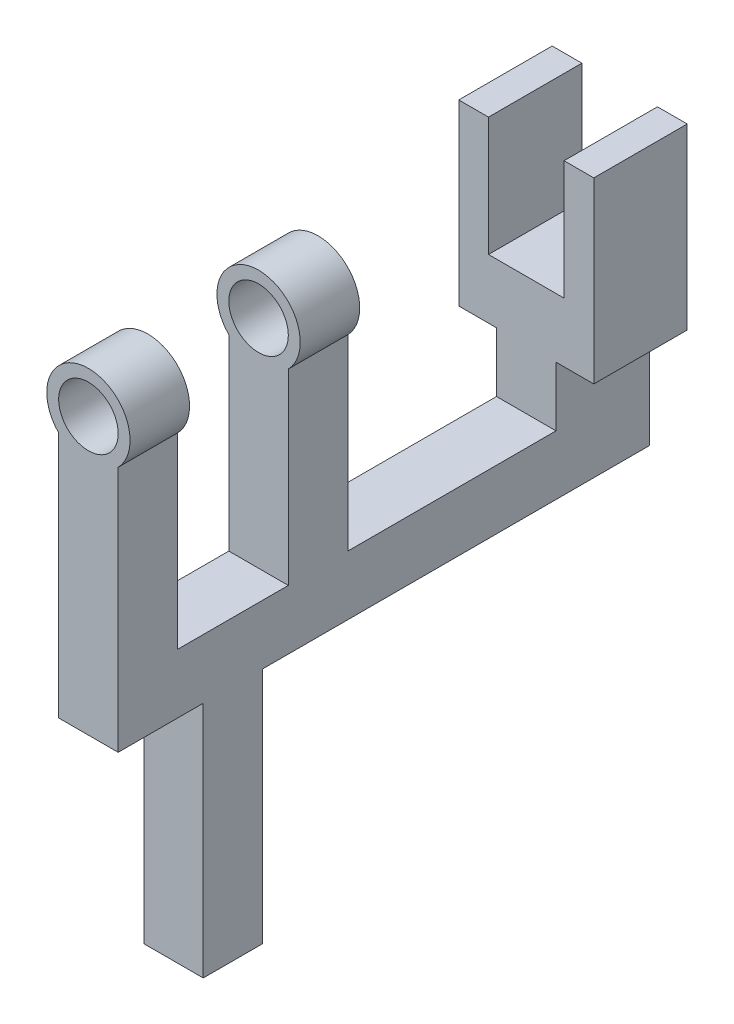
SolidWorks part; units mm, degrees
ref_plane "Front Plane" through (0, 0, 0) normal (0, 0, 1) x (1, 0, 0)
ref_plane "Top Plane" through (0, 0, 0) normal (0, 1, 0) x (1, 0, 0)
ref_plane "Right Plane" through (0, 0, 0) normal (1, 0, 0) x (0, 0, -1)
sketch "Sketch1" plane through (0, 0, 0) normal (0, 0, 1) x (1, 0, 0)
  line L1 (0, 0) -> (-10, 0)
  line L2 (0, 0) -> (0, -10)
  line L3 (0, -10) -> (-10, -10)
  line L4 (-10, 0) -> (-10, -10)
  dimension "D1" = 10
  dimension "D2" = 10
extrude "Boss-Extrude1" add sketch "Sketch1" along normal blind 70 contours L4 L3 L2 L1
sketch "Sketch2" plane through (0, 0, 0) normal (0, 1, 0) x (1, 0, 0)
  line L0 (-10, -70) -> (-10, 0) construction
  line L1 (0, 0) -> (-10, 0)
  line L2 (0, 0) -> (0, -15.7)
  line L3 (0, -15.7) -> (-10, -15.7)
  line L4 (-10, 0) -> (-10, -15.7)
  dimension "D1" = 15.7
extrude "Boss-Extrude2" add sketch "Sketch2" along normal blind 20
sketch "Sketch3" plane through (0, 20, 0) normal (0, 1, 0) x (1, 0, 0)
  line L0 (-10, 0) -> (0, 0)
  line L1 (-10, 0) -> (-11.35, 0)
  line L2 (0, 0) -> (1.35, 0)
  line L4 (-10, 0) -> (-10, -15.7)
  line L5 (-10, -15.7) -> (0, -15.7)
  line L6 (0, -15.7) -> (0, 0)
  line L7 (-11.35, 0) -> (-11.35, -15.7)
  line L8 (-11.35, -15.7) -> (-10, -15.7)
  line L9 (0, -15.7) -> (1.35, -15.7)
  line L10 (1.35, -15.7) -> (1.35, 0)
  line L11 (-11.35, 0) -> (-16.35, 0)
  line L12 (-16.35, 0) -> (-16.35, -15.7)
  line L13 (-16.35, -15.7) -> (-11.35, -15.7)
  line L14 (1.35, 0) -> (6.35, 0)
  line L15 (6.35, 0) -> (6.35, -15.7)
  line L16 (6.35, -15.7) -> (1.35, -15.7)
  point P3 (-5, 0)
  dimension "D1" = 12.7
  dimension "D2" = 5
extrude "Boss-Extrude4" add sketch "Sketch3" along normal blind 20 and the other way blind 10 separate body contours L12 L13 L7 L11 | L16 L15 L14 L10 region at (-13.85, 20, 7.85) region at (3.85, 20, 7.85)
extrude "Boss-Extrude5" add sketch "Sketch3<4>" against normal blind 10 contours L7 L8 L0 L1 | L9 L10 L2 region at (-10.675, 20, 7.85) region at (0.675, 20, 7.85)
sketch "Sketch3<4>" plane through (0, 20, 0) normal (0, 1, 0) x (1, 0, 0) same geometry as "Sketch3"
sketch "Sketch4" plane through (0, 0, 0) normal (0, 1, 0) x (1, 0, 0)
  line L0 (-10, -15.7) -> (-10, -60.7) construction
  line L1 (-10, -70) -> (-10, -15.7) construction
  line L2 (-10, -60.7) -> (0, -60.7)
  line L3 (0, -70) -> (0, -15.7) construction
  line L4 (0, -60.7) -> (0, -50.7)
  line L5 (0, -50.7) -> (-10, -50.7)
  line L6 (-10, -50.7) -> (-10, -60.7)
  dimension "D1" = 45
  dimension "D2" = 10
extrude "Boss-Extrude6" add sketch "Sketch4" along normal blind 40
sketch "Sketch5" plane through (0, 0, 60.7) normal (0, 0, 1) x (1, 0, 0)
  line L0 (-5, 31.4) -> (-5, 0)
  line L3 (-10, 0) -> (0, 0) construction
  line L4 (-5, 29.4) -> (-10, 29.4)
  line L5 (-10, 40) -> (-10, 0) construction
  line L6 (-10, 29.4) -> (-10, 40)
  line L7 (-10, 40) -> (0, 40)
  line L8 (0, 40) -> (0, 29.4)
  line L9 (0, 40) -> (0, 0) construction
  line L10 (0, 29.4) -> (-5, 29.4)
  circle A0 centre (-5, 36.4) radius 5
  circle A2 centre (-5, 36.4) radius 7
  line M7 (0, 40) -> (-10, 40)
  line M8 (-10, 40) -> (-10, 0)
  dimension "D1" = 31.4
  dimension "D2" = 2
  dimension "D3" = 10
extrude "Boss-Extrude8" add sketch "Sketch5" against normal up to surface (10 mm away) contours L8 A2 L6 A0 M8 M7 region at (0.1837, 38.2, 60.7) up to face at (-5, 20, 50.7)
extrude "Cut-Extrude3" cut sketch "Sketch5<7>" against normal up to next contours A0 L7 region at (-5, 36.0124, 60.7)
sketch "Sketch5<7>" plane through (0, 0, 60.7) normal (0, 0, 1) x (1, 0, 0) same geometry as "Sketch5"
mirror "Mirror13" about plane through (0, 0, 70) normal (0, 0, 1) of bodies 127
sketch "Sketch6" plane through (0, 0, 0) normal (0, 1, 0) x (1, 0, 0)
  line L0 (-10, -89.3) -> (-16.35, -89.3)
  line L1 (-16.35, -89.3) -> (-16.35, -140)
  line L2 (-16.35, -140) -> (6.35, -140)
  line L3 (6.35, -140) -> (6.35, -89.3)
  line L4 (6.35, -89.3) -> (-10, -89.3)
extrude "Cut-Extrude4" cut sketch "Sketch6" against normal up to next and the other way up to next
sketch "Sketch7" plane through (0, -10, 0) normal (0, -1, 0) x (1, 0, 0)
  line L0 (-10, 89.3) -> (-10, 50.7) construction
  line L1 (-10, 50.7) -> (0, 50.7) construction
  line L2 (0, 50.7) -> (0, 89.3) construction
  line L3 (0, 89.3) -> (0, 79.3) construction
  line L4 (0, 89.3) -> (0, 0) construction
  line L5 (0, 89.3) -> (-10, 89.3) construction
  line L6 (-10, 70) -> (-10, 75)
  line L7 (-10, 75) -> (0, 75)
  line L8 (0, 75) -> (0, 70)
  line L9 (0, 70) -> (0, 65)
  line L10 (0, 65) -> (-10, 65)
  line L11 (-10, 65) -> (-10, 70)
  dimension "D1" = 10
extrude "Boss-Extrude9" add sketch "Sketch7" along normal blind 40
